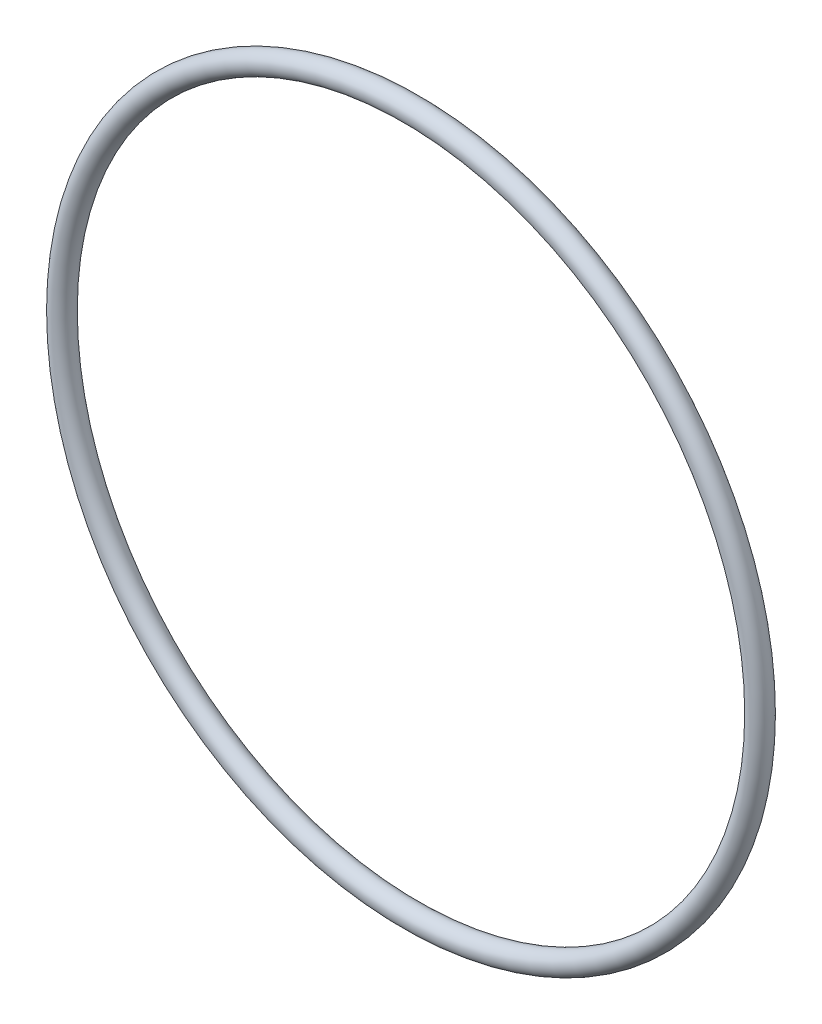
SolidWorks part; units mm, degrees
ref_plane "Front" through (0, 0, 0) normal (0, 0, 1) x (1, 0, 0)
ref_plane "Top" through (0, 0, 0) normal (0, 1, 0) x (1, 0, 0)
ref_plane "Right" through (0, 0, 0) normal (1, 0, 0) x (0, 0, -1)
sketch "Sketch1" plane through (0, 0, 0) normal (0, 0, 1) x (1, 0, 0)
  circle A0 centre (0, 0) radius 28
  dimension "d1" = 56
sketch "Sketch2" plane through (0, 0, 0) normal (0, 1, 0) x (1, 0, 0)
  circle A0 centre (-28.9, 0) radius 0.9
  point P2 (-28, 0)
  dimension "d2" = 1.8
sweep "Sweep1" add profiles "Sketch2" path "Sketch1"
ref_axis "Axis1" through (0, 0, -4.6197) along (0, 0, 1)
